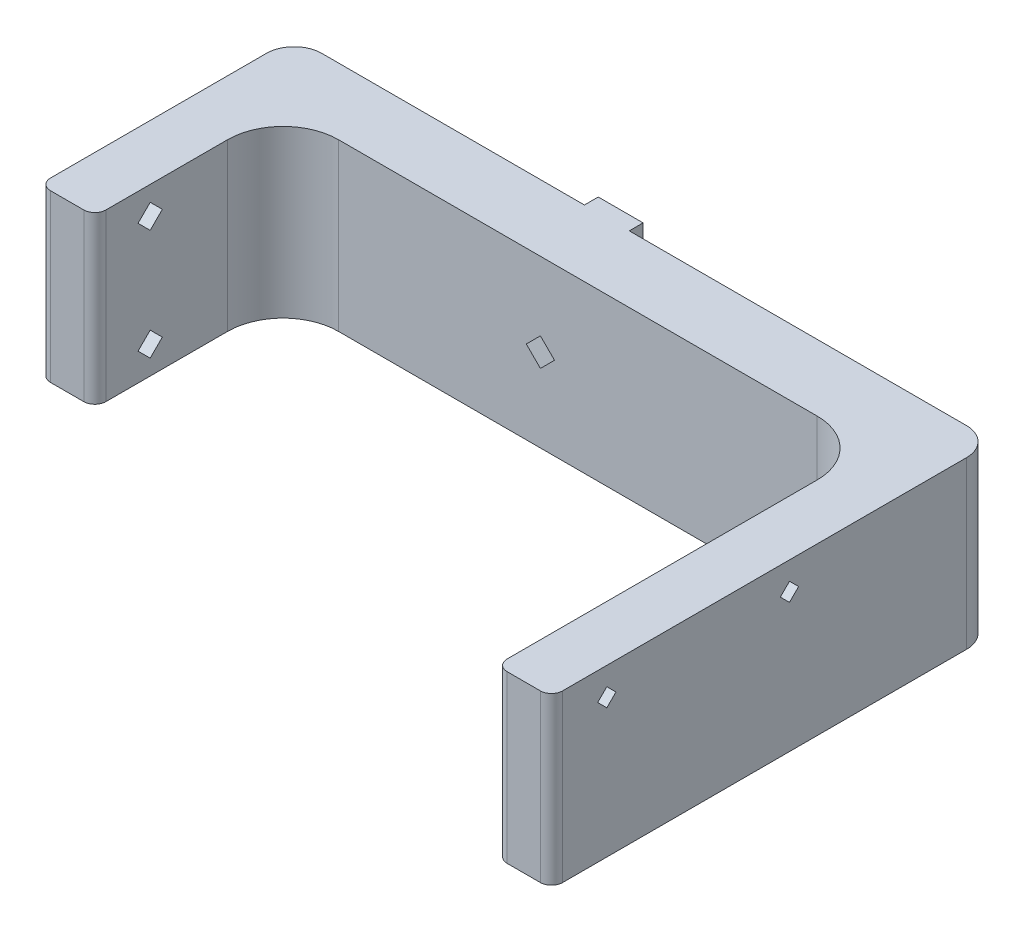
SolidWorks part; units mm, degrees
ref_plane "Ebene vorne" through (0, 0, 0) normal (0, 0, 1) x (1, 0, 0)
ref_plane "Ebene oben" through (0, 0, 0) normal (0, 1, 0) x (1, 0, 0)
ref_plane "Ebene rechts" through (0, 0, 0) normal (1, 0, 0) x (0, 0, -1)
sketch "Skizze1" plane through (0, 0, 0) normal (0, 1, 0) x (1, 0, 0)
  line L0 (-91.0599, 0) -> (138.7496, 0) construction
  line L1 (-56.5, 0) -> (-56.5, -26)
  line L2 (-56.5, 0) -> (-56.5, 20)
  line L3 (-56.5, 20) -> (70, 20)
  line L4 (70, 0) -> (70, 20)
  line L5 (-56.5, -26) -> (-46.5, -26)
  line L6 (70, -60) -> (70, 0)
  line L7 (0, 39.9859) -> (0, -26.2006) construction
  line L8 (-46.5, -26) -> (-46.5, 8)
  line L9 (-46.5, 8) -> (60, 8)
  line L10 (60, -60) -> (60, 8)
  line L11 (60, -60) -> (70, -60)
  point P0 (0, 0)
  point P17 (0, 8)
  dimension "D4" = 10
  dimension "D1" = 56.5
  dimension "D2" = 20
  dimension "D3" = 26
  dimension "D5" = 12
  dimension "D6" = 70
  dimension "D7" = 10
  dimension "D8" = 60
extrude "Aufsatz-Linear austragen1" add sketch "Skizze1" along normal blind 30
sketch "Skizze5" plane through (0, 0, -20) normal (0, 0, -1) x (-1, 0, 0)
  line L0 (-70, 30) -> (56.5, 30) construction
  line L1 (0, 49.8648) -> (0, -19.3679) construction
  line L2 (-4.05, 0) -> (-4.05, 30)
  line L3 (-4.05, 30) -> (4.05, 30)
  line L4 (4.05, 0) -> (4.05, 30)
  line L5 (-4.05, 0) -> (4.05, 0)
  line L6 (-70, 0) -> (56.5, 0) construction
  line L7 (0, 16.5001) -> (0, -16.5001) construction
  point P10 (0, 30)
  point P13 (4.05, 15)
  point P14 (-4.05, 15)
  dimension "D2" = 8.1
extrude "Aufsatz-Linear austragen2" add sketch "Skizze5" along normal blind 3
chamfer "Fase2" distance 0.5 angle 45 4 edges at (-4.05, 15, -23) (0, 0, -23) (4.05, 15, -23) (0, 30, -23)
fillet "Verrundung1" radius 5 2 edges at (70, 15, -20) (-56.5, 15, -20)
fillet "Verrundung2" radius 10 2 edges at (60, 15, -8) (-46.5, 15, -8)
sketch "Skizze8" plane through (60, 0, 0) normal (-1, 0, 0) x (0, 0, 1)
  line L0 (6.209, 25) -> (81.4338, 25) construction
  line L1 (17, 72.048) -> (17, -25.348) construction
  line L2 (50, 46.931) -> (50, -29.8559) construction
  line L3 (17, 26.65) -> (15.35, 25)
  line L4 (15.35, 25) -> (17, 23.35)
  line L5 (17, 23.35) -> (18.65, 25)
  line L6 (18.65, 25) -> (17, 26.65)
  line L7 (48.35, 25) -> (50, 26.65)
  line L8 (50, 26.65) -> (51.65, 25)
  line L9 (51.65, 25) -> (50, 23.35)
  line L10 (50, 23.35) -> (48.35, 25)
  line L11 (45.65, 0) -> (-45.65, 0) construction
  line L12 (0, -16.5001) -> (0, 16.5001) construction
  circle A0 centre (17, 25) radius 1.65 construction
  circle A1 centre (50, 25) radius 1.65 construction
  dimension "D3" = 3.3
  dimension "D1" = 25
  dimension "D2" = 33
  dimension "D4" = 17
extrude "Schnitt-Linear austragen1" cut sketch "Skizze8" against normal through all
fillet "Verrundung3" radius 2 4 edges at (70, 15, 60) (60, 15, 60) (-56.5, 15, 26) (-46.5, 15, 26)
sketch "Skizze9" plane through (0, 0, 0) normal (1, 0, 0) x (0, 0, -1)
  line L0 (-16, 47.3104) -> (-16, -16.795) construction
  line L1 (37.6163, 0) -> (-74.5313, 0) construction
  line L2 (-16, 27.192) -> (-13.808, 25)
  line L3 (-13.808, 25) -> (-16, 22.808)
  line L4 (-16, 22.808) -> (-18.192, 25)
  line L5 (-18.192, 25) -> (-16, 27.192)
  line L6 (-16, 7.192) -> (-13.808, 5)
  line L7 (-13.808, 5) -> (-16, 2.808)
  line L8 (-16, 2.808) -> (-18.192, 5)
  line L9 (-18.192, 5) -> (-16, 7.192)
  circle A1 centre (-16, 5) radius 1.55 construction
  circle A2 centre (-16, 25) radius 1.55 construction
  dimension "D4" = 3.1
  dimension "D1" = 20
  dimension "D2" = 5
  dimension "D3" = 16
extrude "Schnitt-Linear austragen2" cut sketch "Skizze9" against normal through all
sketch "Skizze10" plane through (0, 0, -8) normal (0, 0, 1) x (1, 0, 0)
  line L0 (0, 48.6386) -> (0, -16.1869) construction
  line L1 (-26.2019, 15) -> (33.4669, 15) construction
  line L2 (0, 17.55) -> (2.55, 15)
  line L3 (2.55, 15) -> (0, 12.45)
  line L4 (0, 12.45) -> (-2.55, 15)
  line L5 (-2.55, 15) -> (0, 17.55)
  circle A0 centre (0, 15) radius 2.55 construction
  dimension "D1" = 5.1
  dimension "D2" = 15
extrude "Schnitt-Linear austragen3" cut sketch "Skizze10" against normal through all
ref_axis "Achse1" through (0, -1.5001, 0) along (0, 1, 0)
ref_axis "Achse2" through (0, 0, 64.15) along (0, 0, -1)
